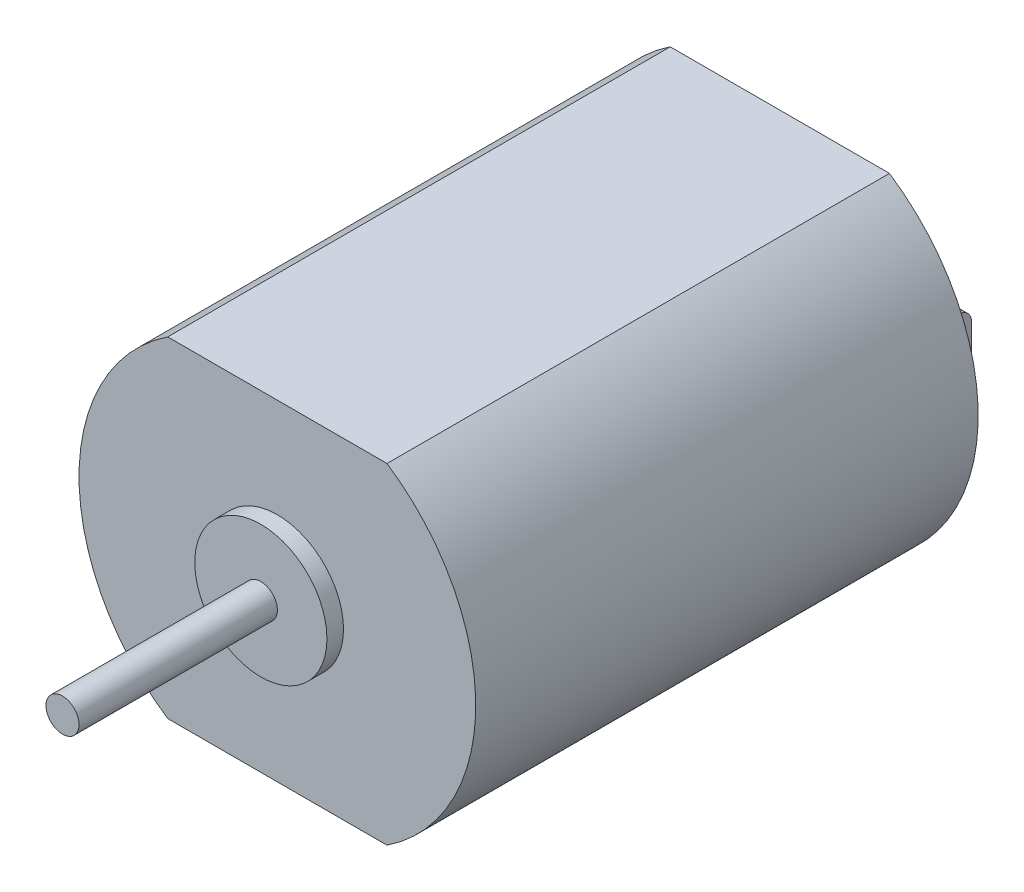
SolidWorks part; units mm, degrees
ref_plane "前视基准面" through (0, 0, 0) normal (0, 0, 1) x (1, 0, 0)
ref_plane "上视基准面" through (0, 0, 0) normal (0, 1, 0) x (1, 0, 0)
ref_plane "右视基准面" through (0, 0, 0) normal (1, 0, 0) x (0, 0, -1)
other "Configuration Table"
sketch "草图1" plane through (0, 0, 0) normal (0, 0, 1) x (1, 0, 0)
  line L0 (3.5, -0.75) -> (3.8, -0.75)
  line L1 (-6, -5) -> (6, -5)
  line L2 (-6, -5) -> (-6, 5)
  line L3 (-6, 5) -> (6, 5)
  line L4 (6, -5) -> (6, 5)
  line L5 (-6, -5) -> (6, 5) construction
  line L6 (-6, 5) -> (6, -5) construction
  line L7 (-3.8, -0.75) -> (-3.5, -0.75)
  line L8 (-3.8, -0.75) -> (-3.8, 0.75)
  line L9 (-3.8, 0.75) -> (-3.5, 0.75)
  line L10 (-3.5, -0.75) -> (-3.5, 0.75)
  line L11 (-3.8, -0.75) -> (-3.5, 0.75) construction
  line L12 (-3.8, 0.75) -> (-3.5, -0.75) construction
  line L13 (3.5, -0.75) -> (3.5, 0.75)
  line L14 (3.5, 0.75) -> (3.8, 0.75)
  line L15 (3.8, -0.75) -> (3.8, 0.75)
  line L16 (-3.5, 0) -> (3.5, 0) construction
  circle A0 centre (0, 0) radius 6
  circle A1 centre (0, 0) radius 2.5
  circle A2 centre (0, 0) radius 1.5
  point P0 (0, 0)
  point P8 (-3.65, 0)
  dimension "D6" = 5
  dimension "D7" = 3
  dimension "D1" = 12
  dimension "D2" = 10
  dimension "D3" = 0.3
  dimension "D4" = 1.5
  dimension "D5" = 7
extrude "凸台-拉伸1" add sketch "草图1" along normal blind 15.2 contours L3 A0 L1 A1 L15 L0 L13 L14 L10 L7 L8 L9 | A1 A2 | A2 | L0 L15 L14 L13 | L7 L10 L9 L8 region at (3.65, 0, 0) region at (-5.1491, -2.7634, 0) region at (-3.65, 0, 0) region at (-2.4293, 0, 0) region at (0, 0, 0)
extrude "凸台-拉伸2" add sketch "草图1<4>" against normal blind 2 contours L13 L14 L15 L0 | L8 L9 L10 L7
sketch "草图1<4>" plane through (0, 0, 0) normal (0, 0, 1) x (1, 0, 0) same geometry as "草图1"
sketch "草图2" plane through (3.8, 0, 0) normal (1, 0, 0) x (0, 0, -1)
  line L0 (0.95, 0) -> (1.05, 0) construction
  line L1 (0.95, 0.45) -> (1.05, 0.45)
  line L2 (0.95, -0.45) -> (1.05, -0.45)
  line L4 (1, 0.75) -> (1, -0.75) construction
  line L5 (2, 0.75) -> (0, 0.75) construction
  line L6 (2, -0.75) -> (0, -0.75) construction
  arc A0 (0.95, 0.45) -> (0.95, -0.45) centre (0.95, 0) ccw
  arc A1 (1.05, -0.45) -> (1.05, 0.45) centre (1.05, 0) ccw
  point P3 (1, 0)
  dimension "D2" = 0.45
  dimension "D1" = 0.1
extrude "切除-拉伸2" cut sketch "草图2" against normal through all
fillet "圆角1" radius 0.4 4 edges at (-3.65, 0.75, -2) (-3.65, -0.75, -2) (3.65, 0.75, -2) (3.65, -0.75, -2)
extrude "凸台-拉伸3" add sketch "草图1<5>" against normal blind 1.2 contours A1 A2 | A2 region at (-2.4293, 0, 0) region at (0, 0, 0)
sketch "草图1<5>" plane through (0, 0, 0) normal (0, 0, 1) x (1, 0, 0) same geometry as "草图1"
extrude "切除-拉伸1" cut sketch "草图1<7>" along normal blind 0.6 from surface contours A2 region at (0, 0, 0) starting at face at (2.5, 0, -1.2)
sketch "草图1<7>" plane through (0, 0, 0) normal (0, 0, 1) x (1, 0, 0) same geometry as "草图1"
fillet "圆角2" radius 0.4 1 edges at (2.5, 0, -1.2)
sketch "草图3" plane through (0, 0, 15.2) normal (0, 0, 1) x (1, 0, 0)
  circle A0 centre (0, 0) radius 2
  circle A1 centre (0, 0) radius 0.5
  dimension "D1" = 4
  dimension "D2" = 1
extrude "凸台-拉伸4" add sketch "草图3" along normal blind 0.5 contours A0
extrude "凸台-拉伸5" add sketch "草图3<3>" along normal blind 6.5 contours A1 region at (0, 0, 15.2)
sketch "草图3<3>" plane through (0, 0, 15.2) normal (0, 0, 1) x (1, 0, 0) same geometry as "草图3"
